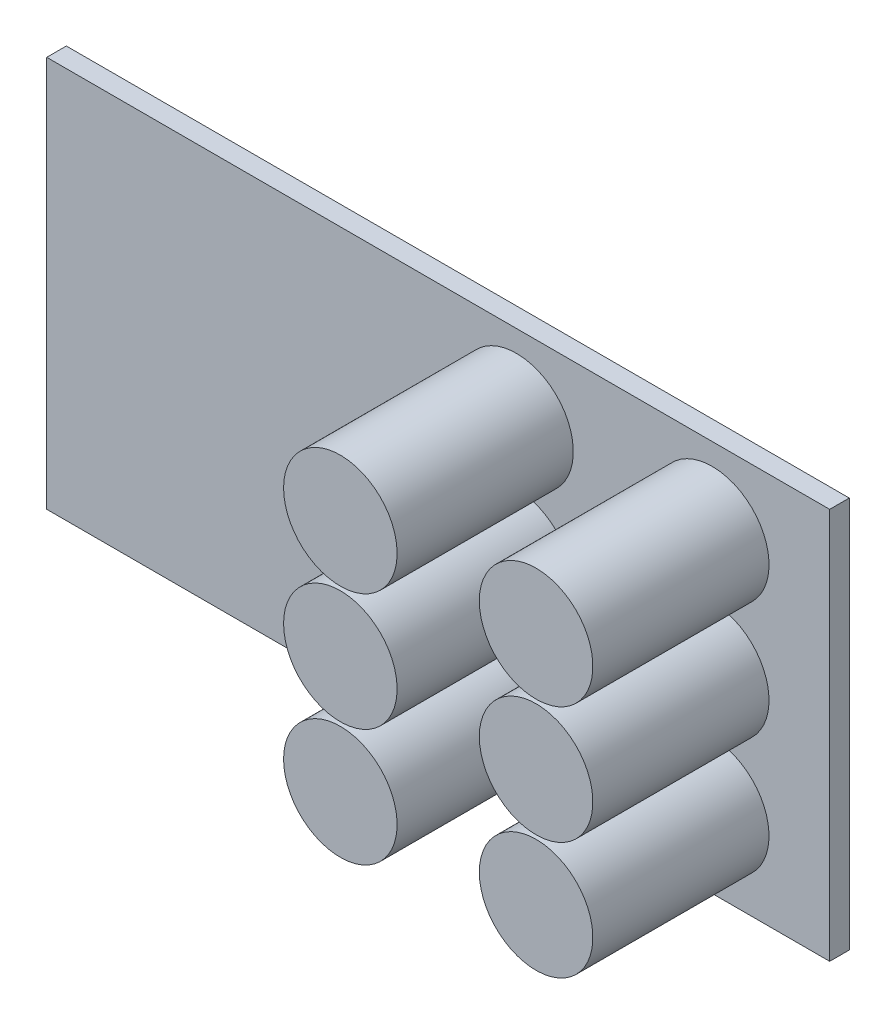
SolidWorks part; units mm, degrees
ref_plane "Plano frontal" through (0, 0, 0) normal (0, 0, 1) x (1, 0, 0)
ref_plane "Plano superior" through (0, 0, 0) normal (0, 1, 0) x (1, 0, 0)
ref_plane "Plano direito" through (0, 0, 0) normal (1, 0, 0) x (0, 0, -1)
sketch "Esboço1" plane through (0, 0, 0) normal (0, 0, 1) x (1, 0, 0)
  line L1 (-100, 50) -> (100, 50)
  line L2 (-100, 50) -> (-100, -50)
  line L3 (-100, -50) -> (100, -50)
  line L4 (100, 50) -> (100, -50)
  line L5 (-100, 50) -> (100, -50) construction
  line L6 (-100, -50) -> (100, 50) construction
  point P0 (0, 0)
  dimension "D1" = 100
  dimension "D2" = 200
extrude "Ressalto-extrusão1" add sketch "Esboço1" along normal blind 5
sketch "Esboço11" plane through (0, 0, 0) normal (0, 0, -1) x (-1, 0, 0)
  line L0 (-100, 50) -> (100, 50) construction
  line L1 (100, -50) -> (-100, -50) construction
  line L2 (-100, -50) -> (-100, 50) construction
  circle A0 centre (-20, -30) radius 12.5
  circle A1 centre (-70, -30) radius 12.5
  circle A2 centre (-70, 0) radius 12.5
  circle A3 centre (-70, 30) radius 12.5
  circle A4 centre (-20, 30) radius 12.5
  circle A5 centre (-20, 0) radius 12.5
  dimension "D1" = 25
  dimension "D2" = 20
  dimension "D3" = 20
  dimension "D4" = 20
  dimension "D5" = 20
  dimension "D6" = 30
  dimension "D7" = 30
  dimension "D8" = 30
  dimension "D9" = 50
  dimension "D10" = 30
  dimension "D11" = 50
  dimension "D12" = 50
  dimension "D13" = 30
sketch "Esboço12" plane through (0, 0, 5) normal (0, 0, 1) x (1, 0, 0)
  circle A0 centre (20, 30) radius 14.5
  circle A1 centre (20, 30) radius 12.5 construction
  circle A2 centre (70, 30) radius 14.5
  circle A3 centre (20, 0) radius 14.5
  circle A4 centre (70, 0) radius 14.5
  circle A5 centre (70, -30) radius 14.5
  circle A6 centre (20, -30) radius 14.5
  dimension "D1" = 2
extrude "Ressalto-extrusão14" add sketch "Esboço12" along normal blind 45 separate body contours A3 | A4 | A0 | A2 | A5 | A6
extrude "Corte-extrusão8" cut sketch "Esboço11" against normal blind 45 contours A3
extrude "Corte-extrusão9" cut sketch "Esboço11<5>" against normal blind 45 contours A1 | A0 | A2 | A4 | A5
sketch "Esboço11<5>" plane through (0, 0, 0) normal (0, 0, -1) x (-1, 0, 0) same geometry as "Esboço11"
